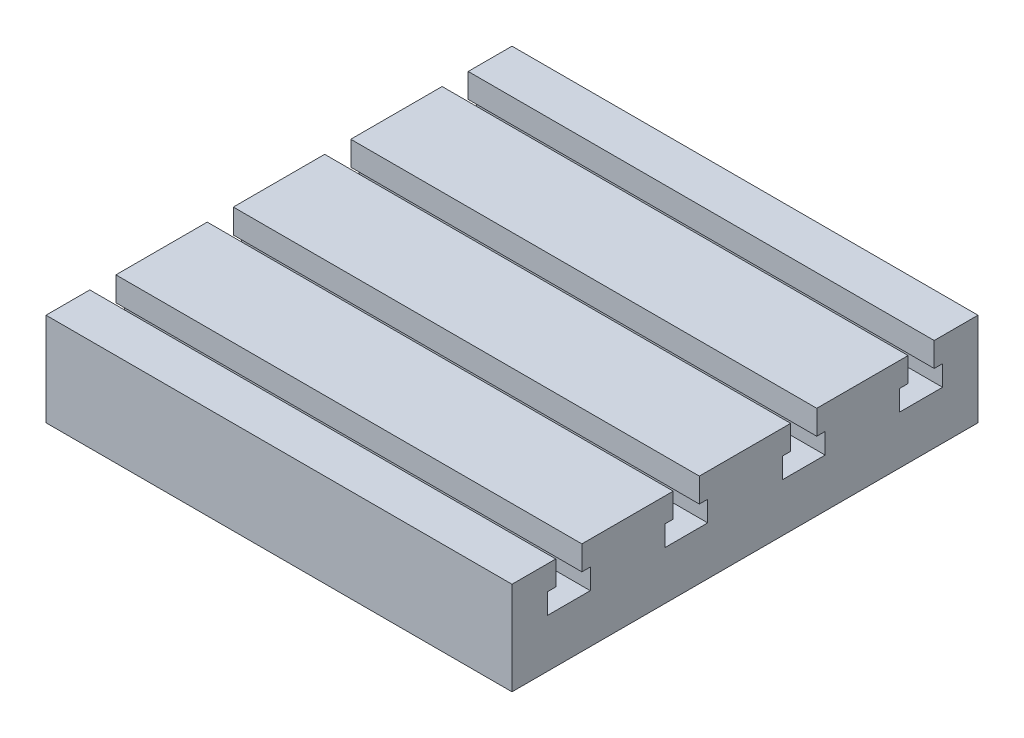
SolidWorks part; units mm, degrees
ref_plane "Alzado" through (0, 0, 0) normal (0, 0, 1) x (1, 0, 0)
ref_plane "Planta" through (0, 0, 0) normal (0, 1, 0) x (1, 0, 0)
ref_plane "Vista lateral" through (0, 0, 0) normal (1, 0, 0) x (0, 0, -1)
sketch "Croquis1" plane through (0, 0, 0) normal (1, 0, 0) x (0, 0, -1)
  line L0 (125, 0) -> (-125, 0)
  line L1 (-125, 0) -> (-125, -50)
  line L2 (-125, -50) -> (125, -50)
  line L3 (125, 0) -> (125, -50)
  dimension "D1" = 50
  dimension "D2" = 125
  dimension "D3" = 125
extrude "Saliente-Extruir1" add sketch "Croquis1" along normal blind 125 and the other way blind 125
sketch "Croquis2" plane through (125, 0, 0) normal (1, 0, 0) x (0, 0, -1)
  line L0 (-101.5, 0) -> (-101.5, -13)
  line L1 (125, 0) -> (-125, 0) construction
  line L2 (-101.5, -13) -> (-106, -13)
  line L3 (-106, -13) -> (-106, -24)
  line L4 (-106, -24) -> (-83, -24)
  line L5 (-83, -24) -> (-83, -13)
  line L6 (-83, -13) -> (-87.5, -13)
  line L7 (-87.5, -13) -> (-87.5, 0)
  line L8 (-101.5, 0) -> (-87.5, 0)
  line L9 (-24.5, 0) -> (-38.5, 0)
  line L10 (-38.5, 0) -> (-38.5, -13)
  line L11 (-38.5, -13) -> (-43, -13)
  line L12 (-43, -13) -> (-43, -24)
  line L13 (-43, -24) -> (-20, -24)
  line L14 (-20, -24) -> (-20, -13)
  line L15 (-20, -13) -> (-24.5, -13)
  line L16 (-24.5, -13) -> (-24.5, 0)
  line L17 (38.5, 0) -> (24.5, 0)
  line L18 (24.5, 0) -> (24.5, -13)
  line L19 (24.5, -13) -> (20, -13)
  line L20 (20, -13) -> (20, -24)
  line L21 (20, -24) -> (43, -24)
  line L22 (43, -24) -> (43, -13)
  line L23 (43, -13) -> (38.5, -13)
  line L24 (38.5, -13) -> (38.5, 0)
  line L25 (101.5, 0) -> (87.5, 0)
  line L26 (87.5, 0) -> (87.5, -13)
  line L27 (87.5, -13) -> (83, -13)
  line L28 (83, -13) -> (83, -24)
  line L29 (83, -24) -> (106, -24)
  line L30 (106, -24) -> (106, -13)
  line L31 (106, -13) -> (101.5, -13)
  line L32 (101.5, -13) -> (101.5, 0)
  line L33 (-94.5, 18.1435) -> (-94.5, -58.5968) construction
  line L34 (-31.5, 13.7374) -> (-31.5, -61.1671) construction
  line L35 (31.5, 18.1435) -> (31.5, -67.042) construction
  line L36 (94.5, 13.7374) -> (94.5, -61.1671) construction
  dimension "D1" = 13
  dimension "D2" = 11
  dimension "D3" = 23
  dimension "D4" = 11.5
  dimension "D5" = 7
  dimension "D6" = 14
  dimension "D7" = 7
  dimension "D8" = 14
  dimension "D9" = 11.5
  dimension "D10" = 23
  dimension "D11" = 7
  dimension "D12" = 14
  dimension "D13" = 11.5
  dimension "D14" = 23
  dimension "D15" = 7
  dimension "D16" = 14
  dimension "D17" = 11.5
  dimension "D18" = 23
  dimension "D19" = 63
  dimension "D20" = 63
  dimension "D21" = 31.5
  dimension "D22" = 31.5
extrude "Cortar-Extruir1" cut sketch "Croquis2" against normal through all
